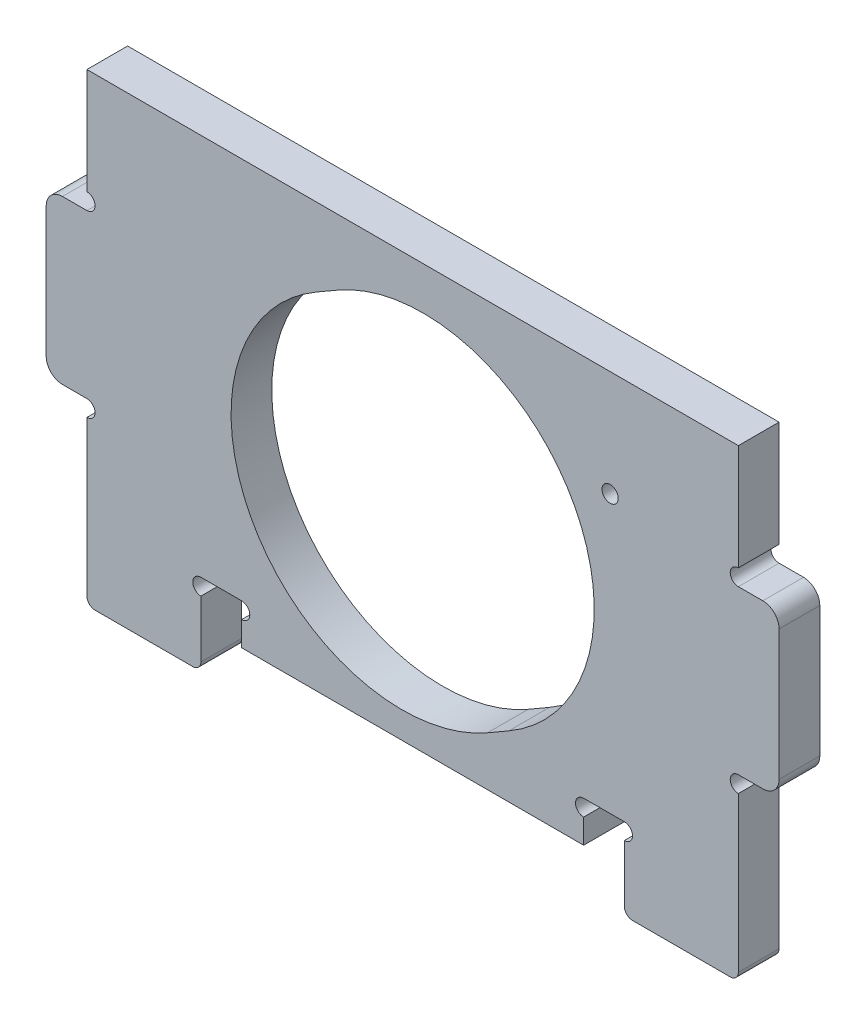
SolidWorks part; units mm, degrees
ref_plane "정면" through (0, 0, 0) normal (0, 0, 1) x (1, 0, 0)
ref_plane "윗면" through (0, 0, 0) normal (0, 1, 0) x (1, 0, 0)
ref_plane "우측면" through (0, 0, 0) normal (1, 0, 0) x (0, 0, -1)
sketch "스케치1" plane through (0, 0, 0) normal (0, 0, 1) x (1, 0, 0)
  line L1 (-50, 17.4622) -> (30, 17.4622)
  line L2 (-50, 17.4622) -> (-50, -34.5378)
  line L3 (-50, -34.5378) -> (30, -34.5378)
  line L4 (30, 17.4622) -> (30, -34.5378)
  dimension "D1" = 80
  dimension "D2" = 52
extrude "보스-돌출1" add sketch "스케치1" along normal blind 5
sketch "스케치7" plane through (0, 0, 0) normal (0, 0, -1) x (-1, 0, 0)
  line L0 (-30, -34.5378) -> (-30, 17.4622) construction
  line L1 (-30, 2.0122) -> (-24, 2.0122)
  line L2 (-30, 2.0122) -> (-30, -1.0878)
  line L3 (-30, -1.0878) -> (-24, -1.0878)
  line L4 (-20, 2.0122) -> (-20, -1.0878) construction
  line L5 (-21.2, -1.0878) -> (-20, -1.0878)
  line L6 (-24, 2.0122) -> (-24, 3.2122)
  line L7 (-24, 3.2122) -> (-21.2, 3.2122) construction
  line L8 (-21.2, 3.2122) -> (-21.2, 2.0122)
  line L9 (-21.2, -1.0878) -> (-21.2, -2.2878)
  line L10 (-21.2, -2.2878) -> (-24, -2.2878) construction
  line L11 (-21.2, 2.0122) -> (-20, 2.0122)
  line L12 (-24, -2.2878) -> (-24, -1.0878)
  line L13 (-30, -22.9878) -> (-24, -22.9878)
  line L14 (-24, 2.0122) -> (-24, -1.0878) construction
  line L15 (-21.2, 2.0122) -> (-21.2, -1.0878) construction
  line L16 (-24, -1.0878) -> (-21.2, -1.0878) construction
  line L17 (-21.2, 2.0122) -> (-24, 2.0122) construction
  line L18 (-30, -22.9878) -> (-30, -26.0878)
  line L19 (-30, -26.0878) -> (-24, -26.0878)
  line L20 (-20, -22.9878) -> (-20, -26.0878) construction
  line L21 (-21.2, -26.0878) -> (-20, -26.0878)
  line L22 (-24, -22.9878) -> (-24, -21.7878)
  line L23 (-24, -21.7878) -> (-21.2, -21.7878) construction
  line L24 (-21.2, -21.7878) -> (-21.2, -22.9878)
  line L25 (-21.2, -26.0878) -> (-21.2, -27.2878)
  line L26 (-21.2, -27.2878) -> (-24, -27.2878) construction
  line L27 (-21.2, -22.9878) -> (-20, -22.9878)
  line L28 (-24, -27.2878) -> (-24, -26.0878)
  line L29 (-24, -22.9878) -> (-24, -26.0878) construction
  line L30 (-21.2, -22.9878) -> (-21.2, -26.0878) construction
  line L31 (-24, -26.0878) -> (-21.2, -26.0878) construction
  line L32 (-21.2, -22.9878) -> (-24, -22.9878) construction
  line L33 (-20, -24.5378) -> (-13.8728, -24.5378) construction
  line L34 (-13.8728, -24.5378) -> (-13.8728, 0.4622) construction
  line L35 (-13.8728, 0.4622) -> (-20, 0.4622) construction
  line L36 (50, -34.5378) -> (-30, -34.5378) construction
  line L37 (10, 17.4622) -> (10, -34.5378) construction
  line L38 (-30, 17.4622) -> (50, 17.4622) construction
  line L39 (33.8728, 0.4622) -> (40, 0.4622) construction
  line L40 (33.8728, -24.5378) -> (33.8728, 0.4622) construction
  line L41 (40, -24.5378) -> (33.8728, -24.5378) construction
  line L42 (41.2, -22.9878) -> (44, -22.9878) construction
  line L43 (44, -26.0878) -> (41.2, -26.0878) construction
  line L44 (41.2, -22.9878) -> (41.2, -26.0878) construction
  line L45 (44, -22.9878) -> (44, -26.0878) construction
  line L46 (41.2, -27.2878) -> (44, -27.2878) construction
  line L47 (44, -21.7878) -> (41.2, -21.7878) construction
  line L48 (40, -22.9878) -> (40, -26.0878) construction
  line L49 (41.2, 2.0122) -> (44, 2.0122) construction
  line L50 (44, -1.0878) -> (41.2, -1.0878) construction
  line L51 (41.2, 2.0122) -> (41.2, -1.0878) construction
  line L52 (44, 2.0122) -> (44, -1.0878) construction
  line L53 (41.2, -2.2878) -> (44, -2.2878) construction
  line L54 (44, 3.2122) -> (41.2, 3.2122) construction
  line L55 (40, 2.0122) -> (40, -1.0878) construction
  line L56 (44, -27.2878) -> (44, -26.0878)
  line L57 (41.2, -22.9878) -> (40, -22.9878)
  line L58 (41.2, -26.0878) -> (41.2, -27.2878)
  line L59 (41.2, -21.7878) -> (41.2, -22.9878)
  line L60 (44, -22.9878) -> (44, -21.7878)
  line L61 (41.2, -26.0878) -> (40, -26.0878)
  line L62 (50, -26.0878) -> (44, -26.0878)
  line L63 (50, -22.9878) -> (50, -26.0878)
  line L64 (50, -22.9878) -> (44, -22.9878)
  line L65 (44, -2.2878) -> (44, -1.0878)
  line L66 (41.2, 2.0122) -> (40, 2.0122)
  line L67 (41.2, -1.0878) -> (41.2, -2.2878)
  line L68 (41.2, 3.2122) -> (41.2, 2.0122)
  line L69 (44, 2.0122) -> (44, 3.2122)
  line L70 (41.2, -1.0878) -> (40, -1.0878)
  line L71 (50, -1.0878) -> (44, -1.0878)
  line L72 (50, 2.0122) -> (50, -1.0878)
  line L73 (50, 2.0122) -> (44, 2.0122)
  arc A0 (-21.2, 3.2122) -> (-24, 3.2122) centre (-22.6, 3.2122) ccw
  arc A1 (-24, -2.2878) -> (-21.2, -2.2878) centre (-22.6, -2.2878) ccw
  arc A2 (-20, -1.0878) -> (-20, 2.0122) centre (-20, 0.4622) ccw
  arc A3 (-21.2, -21.7878) -> (-24, -21.7878) centre (-22.6, -21.7878) ccw
  arc A4 (-24, -27.2878) -> (-21.2, -27.2878) centre (-22.6, -27.2878) ccw
  arc A5 (-20, -26.0878) -> (-20, -22.9878) centre (-20, -24.5378) ccw
  arc A6 (40, -26.0878) -> (40, -22.9878) centre (40, -24.5378) cw
  arc A7 (44, -27.2878) -> (41.2, -27.2878) centre (42.6, -27.2878) cw
  arc A8 (41.2, -21.7878) -> (44, -21.7878) centre (42.6, -21.7878) cw
  arc A9 (40, -1.0878) -> (40, 2.0122) centre (40, 0.4622) cw
  arc A10 (44, -2.2878) -> (41.2, -2.2878) centre (42.6, -2.2878) cw
  arc A11 (41.2, 3.2122) -> (44, 3.2122) centre (42.6, 3.2122) cw
  dimension "D6" = 10
  dimension "D1" = 5.5
  dimension "D2" = 3.1
  dimension "D3" = 3.1
  dimension "D4" = 10
  dimension "D5" = 2.8
  dimension "D7" = 5.5
  dimension "D8" = 2.8
  dimension "D9" = 10
  dimension "D10" = 25
extrude "컷-돌출3" [suppressed] cut sketch "스케치7" against normal blind 10
sketch "스케치8" plane through (0, 0, 0) normal (0, 0, -1) x (-1, 0, 0)
  line L0 (50, 17.4622) -> (50, -34.5378) construction
  line L3 (50, -34.5378) -> (-30, -34.5378) construction
  line L4 (8.701, -8.7878) -> (11.299, -10.2878) construction
  line L5 (19.201, 9.3988) -> (21.799, 7.8988)
  line L6 (-1.799, -26.9743) -> (0.799, -28.4743)
  arc A0 (19.201, 9.3988) -> (-1.799, -26.9743) centre (8.701, -8.7878) ccw
  arc A1 (0.799, -28.4743) -> (21.799, 7.8988) centre (11.299, -10.2878) ccw
  point P9 (10, -9.5378)
  dimension "D1" = 21
  dimension "D2" = 30
  dimension "D3" = 3
  dimension "D4" = 40
  dimension "D5" = 25
extrude "컷-돌출4" cut sketch "스케치8" against normal blind 10
sketch "스케치9" plane through (0, 0, 0) normal (0, 0, -1) x (-1, 0, 0)
  line L0 (10, -9.5378) -> (-14.2487, 4.4622) construction
  line L18 (10, -9.5378) -> (10, 17.4622) construction
  line L19 (-30, 17.4622) -> (50, 17.4622) construction
  circle A1 centre (-14.2487, 4.4622) radius 1
  point P14 (10, -9.5378)
  dimension "D2" = 28
  dimension "D3" = 2
  dimension "D1" = 60
extrude "컷-돌출5" cut sketch "스케치9" against normal blind 10
sketch "스케치10" plane through (0, 0, 5) normal (0, 0, 1) x (1, 0, 0)
  line L0 (-50, -34.5378) -> (30, -34.5378) construction
  line L1 (16, -29.5378) -> (11, -29.5378)
  line L2 (16, -29.5378) -> (16, -34.5378)
  line L3 (16, -34.5378) -> (11, -34.5378)
  line L4 (11, -29.5378) -> (11, -34.5378)
  line L5 (11, -29.5378) -> (11, -34.5378) construction
  line L6 (-36, -29.5378) -> (-36, -34.5378) construction
  line L7 (-31, -29.5378) -> (-36, -29.5378)
  line L8 (-31, -29.5378) -> (-31, -34.5378)
  line L9 (-31, -34.5378) -> (-36, -34.5378)
  line L10 (-36, -29.5378) -> (-36, -34.5378)
extrude "컷-돌출6" cut sketch "스케치10" against normal blind 10
sketch "스케치11" plane through (0, 0, 0) normal (0, 0, -1) x (-1, 0, 0)
  line L0 (-11, -29.5378) -> (-11, -34.5378) construction
  line L1 (-16, -34.5378) -> (-16, -29.5378) construction
  line L2 (31, -34.5378) -> (31, -29.5378) construction
  line L3 (36, -29.5378) -> (36, -34.5378) construction
  circle A0 centre (-11, -30.5378) radius 1
  circle A1 centre (-16, -30.5378) radius 1
  circle A2 centre (31, -30.5378) radius 1
  circle A3 centre (36, -30.5378) radius 1
  dimension "D1" = 2
extrude "컷-돌출7" cut sketch "스케치11" against normal blind 10
sketch "스케치12" plane through (0, 0, 0) normal (0, 0, -1) x (-1, 0, 0)
  line L0 (50, 17.4622) -> (50, -34.5378) construction
  line L1 (50, 2.4622) -> (55, 2.4622)
  line L2 (50, 2.4622) -> (50, -17.5378)
  line L3 (50, -17.5378) -> (55, -17.5378)
  line L4 (55, 2.4622) -> (55, -17.5378)
  line L5 (55, -34.5378) -> (55, -17.5378) construction
  line L8 (10, 17.4622) -> (10, -34.5378) construction
  line L9 (-30, 17.4622) -> (50, 17.4622) construction
  line L10 (31, -34.5378) -> (-11, -34.5378) construction
  line L11 (-35, 2.4622) -> (-35, -17.5378)
  line L12 (-30, -17.5378) -> (-35, -17.5378)
  line L13 (-30, 2.4622) -> (-30, -17.5378)
  line L14 (-30, 2.4622) -> (-35, 2.4622)
  dimension "D1" = 15
  dimension "D2" = 20
extrude "보스-돌출4" add sketch "스케치12" against normal blind 5
sketch "스케치13" plane through (0, 0, 0) normal (0, 0, -1) x (-1, 0, 0)
  line L0 (50, 17.4622) -> (50, 2.4622) construction
  line L3 (50, -17.5378) -> (50, -34.5378) construction
  line L4 (-30, -34.5378) -> (-30, -17.5378) construction
  line L5 (-30, -34.5378) -> (-30, -17.5378) construction
  circle A0 centre (50, 3.4622) radius 1
  circle A1 centre (50, -18.5378) radius 1
  circle A2 centre (-30, 3.4622) radius 1
  circle A3 centre (-30, -18.5378) radius 1
  dimension "D1" = 2
extrude "컷-돌출8" cut sketch "스케치13" against normal blind 5
fillet "필렛2" radius 2 4 edges at (35, -17.5378, 2.5) (35, 2.4622, 2.5) (-55, -17.5378, 2.5) (-55, 2.4622, 2.5)
sketch "스케치14" plane through (0, 0, 0) normal (0, 0, -1) x (-1, 0, 0)
  line L1 (50, -34.5378) -> (36, -34.5378)
  line L2 (50, -34.5378) -> (50, -39.5378)
  line L3 (50, -39.5378) -> (36, -39.5378)
  line L4 (36, -34.5378) -> (36, -39.5378)
  line L5 (-16, -34.5378) -> (-30, -34.5378)
  line L6 (-16, -34.5378) -> (-16, -39.5378)
  line L7 (-16, -39.5378) -> (-30, -39.5378)
  line L8 (-30, -34.5378) -> (-30, -39.5378)
  dimension "D1" = 5
extrude "보스-돌출5" add sketch "스케치14" against normal blind 5
fillet "필렛3" radius 1 4 edges at (30, -39.5378, 2.5) (-36, -39.5378, 2.5) (-50, -39.5378, 2.5) (16, -39.5378, 2.5)
